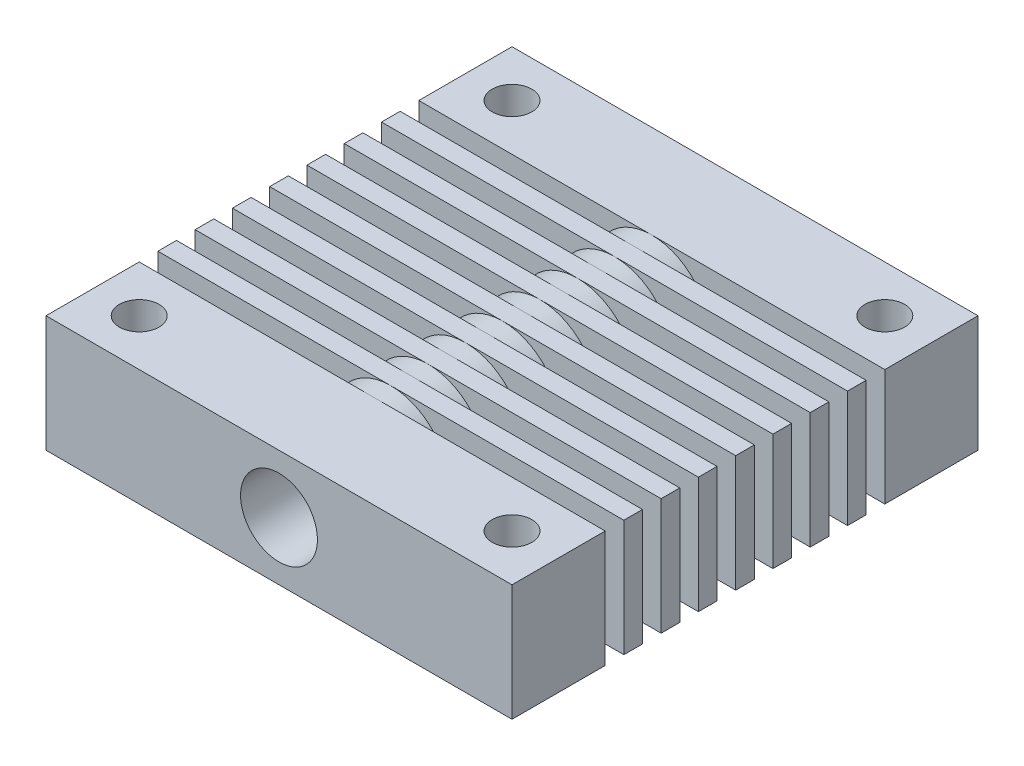
SolidWorks part; units mm, degrees
ref_plane "Plan de face" through (0, 0, 0) normal (0, 0, 1) x (1, 0, 0)
ref_plane "Plan de dessus" through (0, 0, 0) normal (0, 1, 0) x (1, 0, 0)
ref_plane "Plan de droite" through (0, 0, 0) normal (1, 0, 0) x (0, 0, -1)
sketch "Esquisse2" plane through (0, 0, 0) normal (0, 0, 1) x (1, 0, 0)
  line L1 (0, 0) -> (40, 0)
  line L2 (0, 0) -> (0, 10)
  line L3 (0, 10) -> (40, 10)
  line L4 (40, 0) -> (40, 10)
  dimension "D1" = 10
  dimension "D2" = 40
extrude "Boss.-Extru.1" add sketch "Esquisse2" along normal blind 40
sketch "Esquisse5" plane through (0, 0, 40) normal (0, 0, 1) x (1, 0, 0)
  line L0 (40, 0) -> (40, 10) construction
  line L1 (40, 10) -> (0, 10) construction
  circle A0 centre (20, 5) radius 2
  dimension "D1" = 4
  dimension "D2" = 20
  dimension "D3" = 5
hole_wizard "Diamètre du perçage Ø4.1 (4.1)1" positions "Esquisse7" profile "Esquisse6" hole size "Ø4.1" standard "ISO" end condition through all
sketch "Esquisse7" plane through (0, 0, 40) normal (0, 0, 1) x (1, 0, 0)
  point P0 (20, 5)
sketch "Esquisse6" plane through (20, 5, 40) normal (1, 0, 0) x (0, -1, 0)
  line L0 (0, 0) -> (0, 40)
  line L1 (0, 40) -> (2.05, 40)
  line L2 (2.05, 40) -> (2.05, 0)
  line L5 (2.05, 0) -> (0, 0)
  line L11 (0, -6.35) -> (0, 107.95) construction
  dimension "Diamètre du perçage jusqu'au prochain" = 4.1
  dimension "Profondeur du perçage jusqu'au prochain" = 40
hole_wizard "Dégagement M61" positions "Esquisse10" profile "Esquisse9" hole size "M6" standard "ISO"
sketch "Esquisse10" plane through (0, 0, 40) normal (0, 0, 1) x (1, 0, 0)
  point P0 (20, 5)
sketch "Esquisse9" plane through (20, 5, 40) normal (1, 0, 0) x (0, -1, 0)
  line L0 (0, 0) -> (0, 9.9828)
  line L1 (0, 9.9828) -> (3.3, 8)
  line L2 (3.3, 8) -> (3.3, 0)
  line L5 (3.3, 0) -> (0, 0)
  line L10 (0, 9.9828) -> (-3.3, 8) construction
  line L11 (0, -6.35) -> (0, 107.95) construction
  dimension "Diamètre du perçage" = 6.6
  dimension "Profondeur du perçage" = 8
  dimension "Angle de pointe" = 118
hole_wizard "Diamètre du perçage Ø6.0 (6)1" positions "Esquisse14" profile "Esquisse13" hole size "Ø6.0" standard "ISO"
sketch "Esquisse14" plane through (0, 0, 0) normal (0, 0, -1) x (-1, 0, 0)
  point P0 (-20, 5)
sketch "Esquisse13" plane through (20, 5, 0) normal (1, 0, 0) x (0, 1, 0)
  line L0 (0, 0) -> (0, 20)
  line L1 (0, 20) -> (3.05, 20)
  line L2 (3.05, 20) -> (3.05, 0)
  line L5 (3.05, 0) -> (0, 0)
  line L10 (0, 20) -> (-3.05, 20) construction
  line L11 (0, -6.35) -> (0, 107.95) construction
  dimension "Diamètre du perçage" = 6.1
  dimension "Profondeur du perçage" = 20
  dimension "Angle de pointe" = 180
sketch "Esquisse15" plane through (0, 0, 0) normal (0, -1, 0) x (1, 0, 0)
  line L0 (0, 40) -> (40, 40) construction
  line L1 (0, 40) -> (0, 0) construction
  line L2 (40, 40) -> (40, 0) construction
  line L3 (0, 0) -> (40, 0) construction
  circle A0 centre (4, 36) radius 1.5
  circle A1 centre (36, 36) radius 1.5
  circle A2 centre (36, 4) radius 1.5
  circle A3 centre (4, 4) radius 1.5
  circle A4 centre (20, 4) radius 1.5
  dimension "D1" = 3
  dimension "D2" = 3
  dimension "D3" = 3
  dimension "D4" = 3
  dimension "D5" = 3
  dimension "D14" = 4
  dimension "D6" = 4
  dimension "D7" = 4
  dimension "D8" = 4
  dimension "D9" = 4
  dimension "D10" = 4
  dimension "D11" = 4
  dimension "D12" = 4
  dimension "D13" = 4
  dimension "D15" = 20
hole_wizard "Dégagement M31" positions "Esquisse17" profile "Esquisse16" hole size "M3" standard "ISO" end condition through all
sketch "Esquisse17" plane through (0, 0, 0) normal (0, -1, 0) x (-1, 0, 0)
  point P0 (-4, -36)
  point P3 (-36, -36)
  point P6 (-36, -4)
  point P9 (-4, -4)
sketch "Esquisse16" plane through (4, 0, 36) normal (1, 0, 0) x (0, 0, -1)
  line L0 (0, 0) -> (0, 10)
  line L1 (0, 10) -> (1.7, 10)
  line L2 (1.7, 10) -> (1.7, 0)
  line L5 (1.7, 0) -> (0, 0)
  line L11 (0, -6.35) -> (0, 107.95) construction
  dimension "Diamètre du perçage jusqu'au prochain" = 3.4
  dimension "Profondeur du perçage jusqu'au prochain" = 10
hole_wizard "Dégagement M32" positions "Esquisse19" profile "Esquisse18" hole size "M3" standard "ISO"
sketch "Esquisse19" plane through (0, 0, 0) normal (0, -1, 0) x (-1, 0, 0)
  point P0 (-20, -4)
sketch "Esquisse18" plane through (20, 0, 4) normal (1, 0, 0) x (0, 0, -1)
  line L0 (0, 0) -> (0, 5)
  line L1 (0, 5) -> (1.7, 5)
  line L2 (1.7, 5) -> (1.7, 0)
  line L5 (1.7, 0) -> (0, 0)
  line L10 (0, 5) -> (-1.7, 5) construction
  line L11 (0, -6.35) -> (0, 107.95) construction
  dimension "Diamètre du perçage" = 3.4
  dimension "Profondeur du perçage" = 5
  dimension "Angle de pointe" = 180
chamfer "Chanfrein1" [suppressed] distance 0.5 angle 45
sketch "Esquisse20" plane through (0, 40, 40) normal (0, 0, -1) x (-1, 0, 0)
  circle A0 centre (-20, -35) radius 5
  circle A1 centre (-20, -35) radius 26.1933
  dimension "D1" = 10
extrude "Enlèv. mat.-Extru.1" cut sketch "Esquisse20" along normal blind 1.6 from offset 8
pattern_linear "Répétition linéaire1" count 8 spacing 3.2 along (0, 0, -1) of "Enlèv. mat.-Extru.1"
